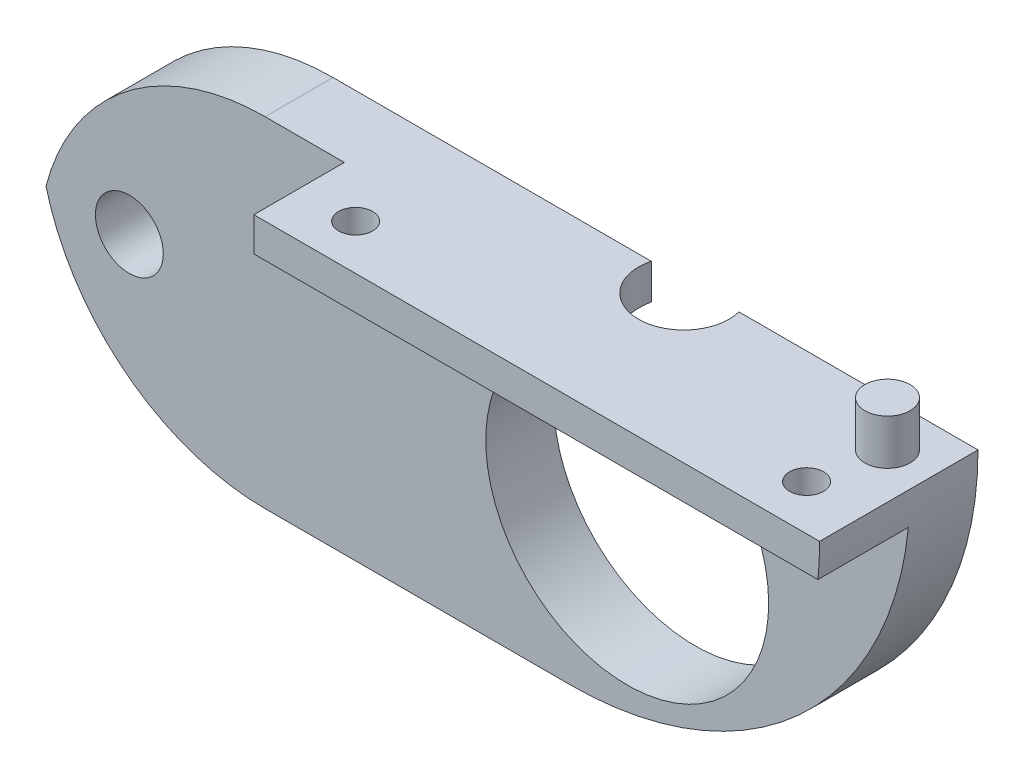
SolidWorks part; units mm, degrees
ref_plane "Plan de face" through (0, 0, 0) normal (0, 0, 1) x (1, 0, 0)
ref_plane "Plan de dessus" through (0, 0, 0) normal (0, 1, 0) x (1, 0, 0)
ref_plane "Plan de droite" through (0, 0, 0) normal (1, 0, 0) x (0, 0, -1)
sketch "Esquisse1" plane through (0, 0, 0) normal (0, 0, 1) x (1, 0, 0)
  line L1 (0, 0) -> (-77, 0)
  line L2 (0, 0) -> (0, 30)
  line L3 (0, 30) -> (-77, 30)
  line L4 (-77, 0) -> (-77, 30)
  dimension "D1" = 77
  dimension "D2" = 30
extrude "Boss.-Extru.1" add sketch "Esquisse1" along normal blind 6
sketch "Esquisse2" plane through (0, 0, 6) normal (0, 0, 1) x (1, 0, 0)
  line L0 (0, 0) -> (0, 30) construction
  line L1 (-77, 0) -> (0, 0) construction
  circle A0 centre (-25, 15) radius 12.5
  circle A1 centre (-69, 15) radius 3
  dimension "D1" = 25
  dimension "D4" = 15
  dimension "D6" = 6
  dimension "D2" = 25
  dimension "D3" = 15
  dimension "D5" = 44
extrude "Enlèv. mat.-Extru.1" cut sketch "Esquisse2" against normal blind 6
sketch "Esquisse3" plane through (0, 0, 6) normal (0, 0, 1) x (1, 0, 0)
  line L1 (0, 30) -> (-50, 30)
  line L2 (0, 30) -> (0, 27)
  line L3 (0, 27) -> (-50, 27)
  line L4 (-50, 30) -> (-50, 27)
  dimension "D1" = 3
  dimension "D2" = 50
extrude "Boss.-Extru.2" add sketch "Esquisse3" along normal blind 8
sketch "Esquisse5" plane through (0, 30, 0) normal (0, 1, 0) x (1, 0, 0)
  line L1 (0, -14) -> (0, 0) construction
  line L2 (0, 0) -> (-77, 0) construction
  circle A0 centre (-25, -1) radius 4
  dimension "D1" = 8
  dimension "D2" = 25
  dimension "D3" = 1
extrude "Enlèv. mat.-Extru.2" cut sketch "Esquisse5" against normal up to next
fillet "Congé1" radius 20 2 edges at (-77, 30, 3) (-77, 0, 3)
fillet "Congé2" radius 30 1 edges at (0, 0, 3)
sketch "Esquisse6" plane through (0, 30, 0) normal (0, 1, 0) x (1, 0, 0)
  line L0 (0, 0) -> (-21.127, 0) construction
  line L2 (0, -14) -> (0, 0) construction
  circle A0 centre (-4, -4) radius 2
  dimension "D1" = 4
  dimension "D2" = 4
  dimension "D3" = 4
extrude "Boss.-Extru.3" add sketch "Esquisse6" along normal blind 4
sketch "Esquisse7" plane through (0, 27, 0) normal (0, -1, 0) x (1, 0, 0)
  line L0 (-50, 14) -> (-50, 6) construction
  line L2 (-50, 14) -> (-0.1504, 14) construction
  line L3 (-0.1504, 6) -> (-0.1504, 14) construction
  circle A0 centre (-45, 10) radius 1.5
  circle A1 centre (-5.1504, 10) radius 1.5
  dimension "D1" = 4
  dimension "D2" = 3
  dimension "D3" = 3
  dimension "D4" = 5
  dimension "D5" = 5
  dimension "D6" = 4
extrude "Enlèv. mat.-Extru.3" cut sketch "Esquisse7" against normal blind 10
